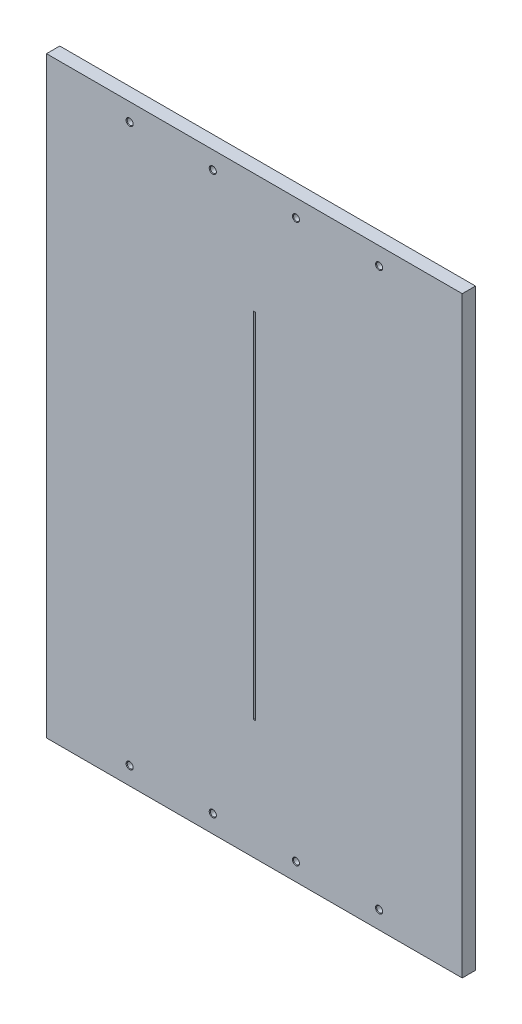
SolidWorks part; units mm, degrees
material "3.0205 (EN-AW 1200)"
ref_plane "Piano frontale" through (0, 0, 0) normal (0, 0, 1) x (1, 0, 0)
ref_plane "Piano superiore" through (0, 0, 0) normal (0, 1, 0) x (1, 0, 0)
ref_plane "Piano destro" through (0, 0, 0) normal (1, 0, 0) x (0, 0, -1)
sketch "Schizzo1" plane through (0, 0, 0) normal (0, 0, 1) x (1, 0, 0)
  line L1 (-235, -335) -> (235, -335)
  line L2 (-235, -335) -> (-235, 335)
  line L3 (-235, 335) -> (235, 335)
  line L4 (235, -335) -> (235, 335)
  line L5 (-235, -335) -> (235, 335) construction
  line L6 (-235, 335) -> (235, -335) construction
  point P0 (0, 0)
  dimension "D1" = 470
  dimension "D2" = 670
extrude "Estrusione-Estrusione1" add sketch "Schizzo1" along normal blind 15
hole_wizard "Foro filettato M8-1" positions "Schizzo8" profile "Schizzo10" tap size "M8" standard "ISO"
sketch "Schizzo8" plane through (0, 0, 15) normal (0, 0, 1) x (1, 0, 0)
  line L0 (-235, 315) -> (235, 315) construction
  line L1 (-235, 335) -> (-235, -335) construction
  line L2 (235, -335) -> (235, 335) construction
  line L4 (235, 335) -> (-235, 335) construction
  line L6 (-235, -315) -> (235, -315) construction
  line L8 (-235, -335) -> (235, -335) construction
  line L9 (-141, 315) -> (-141, -315) construction
  line L11 (-47, 315) -> (-47, -315) construction
  line L13 (47, 315) -> (47, -315) construction
  line L15 (141, 315) -> (141, -315) construction
  point P0 (-141, 315)
  point P2 (-47, 315)
  point P4 (47, 315)
  point P6 (141, 315)
  point P8 (-141, -315)
  point P10 (-47, -315)
  point P14 (141, -315)
  point P16 (47, -315)
  dimension "D1" = 20
  dimension "D2" = 20
  dimension "D3" = 94
  dimension "D4" = 94
  dimension "D5" = 94
  dimension "D6" = 94
sketch "Schizzo10" plane through (-141, 315, 15) normal (1, 0, 0) x (0, -1, 0)
  line L0 (0, 0) -> (0, 24.2929)
  line L1 (0, 24.2929) -> (3.4, 22.25)
  line L2 (3.4, 22.25) -> (3.4, 0.625)
  line L3 (3.4, 0.625) -> (4.025, 0)
  line L5 (4.025, 0) -> (0, 0)
  line L6 (-3.4, 0.625) -> (-4.025, 0) construction
  line L10 (0, 24.2929) -> (-3.4, 22.25) construction
  line L11 (0, -6.35) -> (0, 107.95) construction
  dimension "Tap Drill Dia." = 6.8
  dimension "Tap Drill Depth" = 22.25
  dimension "Near C'Sink Dia." = 8.05
  dimension "Near C'Sink Angle" = 90
  dimension "Drill Angle" = 118
cosmetic thread "Filettatura del foro1" parameters "D1"=16, "D2"=8
cosmetic thread "Filettatura del foro2" parameters "D1"=16, "D2"=8
cosmetic thread "Filettatura del foro3" parameters "D1"=16, "D2"=8
cosmetic thread "Filettatura del foro4" parameters "D1"=16, "D2"=8
cosmetic thread "Filettatura del foro5" parameters "D1"=16, "D2"=8
cosmetic thread "Filettatura del foro6" parameters "D1"=16, "D2"=8
cosmetic thread "Filettatura del foro7" parameters "D1"=16, "D2"=8
cosmetic thread "Filettatura del foro8" parameters "D1"=16, "D2"=8
sketch "Schizzo11" plane through (0, 0, 15) normal (0, 0, 1) x (1, 0, 0)
  line L1 (-1, 200) -> (1, 200)
  line L2 (-1, 200) -> (-1, -200)
  line L3 (-1, -200) -> (1, -200)
  line L4 (1, 200) -> (1, -200)
  line L5 (-1, 200) -> (1, -200) construction
  line L6 (-1, -200) -> (1, 200) construction
  point P0 (0, 0)
  dimension "D1" = 400
  dimension "D2" = 2
extrude "Taglio-Estrusione1" cut sketch "Schizzo11" against normal blind 5
